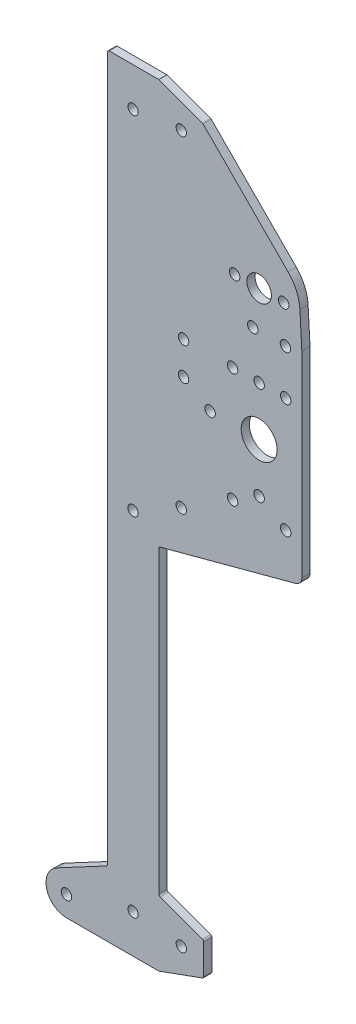
SolidWorks part; units mm, degrees
ref_plane "Front Plane" through (0, 0, 0) normal (0, 0, 1) x (1, 0, 0)
ref_plane "Top Plane" through (0, 0, 0) normal (0, 1, 0) x (1, 0, 0)
ref_plane "Right Plane" through (0, 0, 0) normal (1, 0, 0) x (0, 0, -1)
sketch "Sketch1" plane through (0, 0, 0) normal (0, 0, 1) x (1, 0, 0)
  line L1 (-10, 150) -> (10, 150)
  line L2 (-10, 150) -> (-10, -150)
  line L3 (-10, -150) -> (10, -150)
  line L4 (10, 150) -> (10, -150)
  line L5 (-10, 150) -> (10, -150) construction
  line L6 (-10, -150) -> (10, 150) construction
  point P0 (0, 0)
  dimension "D1" = 300
  dimension "20mm" = 20
extrude "Boss-Extrude1" add sketch "Sketch1" along normal blind 3.175
sketch "Sketch2" plane through (0, 0, 3.175) normal (0, 0, 1) x (1, 0, 0)
  line L0 (10, 150) -> (27.4625, 143.65)
  line L1 (27.4625, 143.65) -> (27.4625, 130.95)
  line L2 (27.4625, 130.95) -> (10, 124.6)
  line L3 (10, -150) -> (10, 150) construction
  line L4 (10, 124.6) -> (10, 150)
  line L5 (10, 150) -> (-10, 150) construction
  line L6 (-10, 0) -> (10, 0) construction
  line L7 (-10, 150) -> (-10, -150) construction
  line L8 (10, -124.6) -> (10, -150)
  line L9 (27.4625, -130.95) -> (10, -124.6)
  line L10 (27.4625, -143.65) -> (27.4625, -130.95)
  line L11 (10, -150) -> (27.4625, -143.65)
  line L12 (18.7312, 140.475) -> (18.7312, 134.125) construction
  circle A1 centre (18.7312, 134.125) radius 5 construction
  circle A2 centre (18.7312, 140.475) radius 2 construction
  circle A4 centre (18.7312, -134.125) radius 5 construction
  circle A5 centre (18.7312, -134.125) radius 2 construction
  circle A6 centre (18.7312, 137.3) radius 2
  circle A7 centre (18.7312, -137.3) radius 2
  point P3 (27.4625, 137.3)
  point P8 (10, 137.3)
  point P13 (18.7312, 127.775)
  point P31 (27.4625, -137.3)
  dimension "D3" = 4
  dimension "D4" = 10
  dimension "D1" = 17.4625
  dimension "2.5" = 25.4
  dimension "D2" = 12.7
  dimension "D5" = 9.525
  dimension "D6" = 9.525
extrude "Boss-Extrude2" add sketch "Sketch2" against normal up to surface (3.175 mm away) up to face at (0, 0, 0)
sketch "Sketch4" plane through (0, 0, 3.175) normal (0, 0, 1) x (1, 0, 0)
  line L0 (0, 150) -> (0, 135) construction
  line L2 (0, 135) -> (0, 0) construction
  line L3 (0, 0) -> (0, -135) construction
  line L4 (0, -135) -> (0, -150) construction
  line L6 (10, 150) -> (-10, 150) construction
  line L7 (-10, -150) -> (10, -150) construction
  circle A0 centre (0, -135) radius 2
  circle A1 centre (0, 0) radius 2
  circle A2 centre (0, 135) radius 2
  dimension "D4" = 4
  dimension "D1" = 15
  dimension "D2" = 135
  dimension "D3" = 135
extrude "Cut-Extrude1" cut sketch "Sketch4" against normal through all
sketch "Sketch5" plane through (0, 0, 3.175) normal (0, 0, 1) x (1, 0, 0)
  line L0 (-10, 111.9) -> (-41.75, 118.25)
  line L1 (-10, 150) -> (-10, -150) construction
  line L2 (-41.75, 118.25) -> (-41.75, 137.3)
  line L3 (-41.75, 137.3) -> (-10, 137.3)
  line L4 (-10, 137.3) -> (-10, 111.9)
  line L5 (10, 150) -> (-10, 150) construction
  line L6 (-41.75, 133.3313) -> (-37.7813, 133.3313) construction
  line L7 (-13.9688, 133.3313) -> (-10, 133.3313) construction
  line L8 (-10, -150) -> (-25.875, -150)
  line L9 (-29.6103, -135.0588) -> (-10, -124.6)
  line L10 (-10, -124.6) -> (-10, -150)
  circle A0 centre (-13.9688, 133.3313) radius 2.032
  circle A1 centre (-13.9688, 122.2188) radius 2.032
  circle A2 centre (-37.7813, 133.3313) radius 2.032
  circle A3 centre (-37.7813, 122.2188) radius 2.032
  arc A4 (-25.875, -150) -> (-29.6103, -135.0588) centre (-25.875, -142.0625) cw
  circle A5 centre (-25.875, -142.0625) radius 2.032
  point P24 (-25.875, 137.3)
  dimension "D5" = 4.064
  dimension "D9" = 4.064
  dimension "D10" = 7.9375
  dimension "D1" = 12.7
  dimension "D2" = 19.05
  dimension "D3" = 25.4
  dimension "D4" = 31.75
  dimension "D6" = 11.1125
  dimension "D7" = 23.8125
  dimension "D8" = 3.9688
  dimension "D11" = 25.4
extrude "Boss-Extrude3" [suppressed] add sketch "Sketch5" against normal up to surface (1.5875 mm away) up to face at (2, -135, 0)
fillet "Fillet3" [suppressed] radius 1.5875
sketch "Sketch6" plane through (0, 0, 3.175) normal (0, 0, 1) x (1, 0, 0)
  line L0 (-10, -124.6) -> (-10, -150) construction
  line L1 (-10, -150) -> (-25.875, -150) construction
  line L2 (-29.6103, -135.0588) -> (-10, -124.6) construction
  line L3 (-10, -124.6) -> (-10, -150)
  line L4 (-10, -150) -> (-25.875, -150)
  line L5 (-29.6103, -135.0588) -> (-10, -124.6)
  circle A0 centre (-25.875, -142.0625) radius 2.032 construction
  arc A1 (-29.6103, -135.0588) -> (-25.875, -150) centre (-25.875, -142.0625) ccw construction
  circle A2 centre (-25.875, -142.0625) radius 2.032
  arc A3 (-29.6103, -135.0588) -> (-25.875, -150) centre (-25.875, -142.0625) ccw
extrude "Boss-Extrude4" add sketch "Sketch6" against normal up to vertex (3.175 mm away) up to point (-10, -150, 0)
fillet "Fillet4" radius 0.7937 8 edges at (10, 124.6, 1.5875) (27.4625, 130.95, 1.5875) (-10, 150, 1.5875) (27.4625, 143.65, 1.5875) (-10, -124.6, 1.5875) (10, -124.6, 1.5875) (27.4625, -130.95, 1.5875) (27.4625, -143.65, 1.5875)
fillet "Fillet5" [suppressed] radius 1.5875
sketch "Sketch7" plane through (0, 0, 0) normal (0, 0, -1) x (-1, 0, 0)
  line L0 (-27.1212, 143.7462) -> (-65.2212, 117.3147)
  line L1 (-65.5625, 116.6625) -> (-65.5625, 10.1095)
  line L2 (-63.2093, 7.0427) -> (-10, -7.2147)
  line L4 (-10, -7.2147) -> (-10, 124.044)
  line L5 (-27.4625, 143.094) -> (-27.4625, 131.506) construction
  line L6 (-26.94, 130.76) -> (-10.5225, 124.79) construction
  line L7 (-27.4625, 143.094) -> (-27.4625, 131.506)
  line L8 (-26.94, 130.76) -> (-10.5225, 124.79)
  line L9 (-10, 150) -> (9.2063, 150) construction
  line L10 (-10, 150) -> (9.2063, 150) construction
  line L11 (-48.989, 45.225) -> (-48.989, 48.4) construction
  line L12 (-38.6703, 23) -> (-59.3078, 23) construction
  line L13 (-38.6703, 23) -> (-38.6703, 67.45) construction
  line L14 (-38.6703, 67.45) -> (-59.3078, 67.45) construction
  line L15 (-59.3078, 23) -> (-59.3078, 67.45) construction
  line L16 (-38.6703, 23) -> (-59.3078, 67.45) construction
  line L17 (-38.6703, 67.45) -> (-59.3078, 23) construction
  line L18 (-48.989, 99.2) -> (-48.989, 48.4) construction
  line L19 (-10, -124.044) -> (-10, 124.044) construction
  arc A0 (-65.2212, 117.3147) -> (-65.5625, 116.6625) centre (-64.7688, 116.6625) ccw
  arc A1 (-65.5625, 10.1095) -> (-63.2093, 7.0427) centre (-62.3875, 10.1095) ccw
  arc A2 (-26.94, 143.84) -> (-27.4625, 143.094) centre (-26.6688, 143.094) ccw construction
  arc A3 (-27.4625, 131.506) -> (-26.94, 130.76) centre (-26.6688, 131.506) ccw construction
  arc A4 (-10, 124.044) -> (-10.5225, 124.79) centre (-10.7937, 124.044) ccw construction
  arc A5 (-27.1212, 143.7462) -> (-27.4625, 143.094) centre (-26.6688, 143.094) ccw
  arc A6 (-27.4625, 131.506) -> (-26.94, 130.76) centre (-26.6688, 131.506) ccw
  arc A7 (-10, 124.044) -> (-10.5225, 124.79) centre (-10.7937, 124.044) ccw
  arc A8 (10, 149.2063) -> (9.2063, 150) centre (9.2063, 149.2063) ccw construction
  circle A9 centre (-48.989, 99.2) radius 4.7625
  circle A10 centre (-48.989, 48.4) radius 6.985
  circle A11 centre (-59.3078, 67.45) radius 2.032
  circle A12 centre (-59.3078, 23) radius 2.032
  circle A13 centre (-38.6703, 23) radius 2.032
  circle A14 centre (-38.6703, 67.45) radius 2.032
  circle A15 centre (-18.7312, 10.3) radius 2.032
  point P32 (-48.989, 45.225)
  point P45 (-18.7312, 137.3)
  dimension "D4" = 9.525
  dimension "D6" = 13.97
  dimension "D11" = 4.064
  dimension "D15" = 3.175
  dimension "D1" = 38.1
  dimension "D2" = 106.553
  dimension "D3" = 16.5735
  dimension "D5" = 50.8
  dimension "D7" = 3.175
  dimension "D8" = 44.45
  dimension "D9" = 50.8
  dimension "D10" = 20.6375
  dimension "D12" = 75
  dimension "D13" = 127
  dimension "D14" = 33.3375
extrude "Boss-Extrude5" add sketch "Sketch7" against normal up to surface (3.175 mm away) up to face at (2, -135, 3.175)
sketch "Sketch8" plane through (0, 0, 3.175) normal (0, 0, 1) x (1, 0, 0)
  line L0 (48.989, 48.4) -> (48.989, 67.45) construction
  line L1 (48.989, 48.4) -> (29.939, 48.4) construction
  line L2 (48.989, 48.4) -> (48.989, 29.35) construction
  line L3 (48.989, 99.2) -> (58.514, 99.2) construction
  line L4 (48.989, 99.2) -> (39.464, 99.2) construction
  line L5 (19.6203, 67.45) -> (19.6203, 54.75) construction
  circle A0 centre (48.989, 67.45) radius 2.032
  circle A1 centre (29.939, 48.4) radius 2.032
  circle A2 centre (48.989, 29.35) radius 2.032
  circle A3 centre (59.3078, 67.45) radius 2.032 construction
  circle A4 centre (58.514, 99.2) radius 2.032
  circle A5 centre (39.464, 99.2) radius 2.032
  circle A6 centre (19.6203, 54.75) radius 2.032
  circle A7 centre (19.6203, 67.45) radius 2.032
  point P20 (40.9949, 94.0213)
  point P21 (58.3131, 101.1458)
  dimension "D2" = 9.525
  dimension "D1" = 19.05
  dimension "D3" = 12.7
  dimension "D4" = 6.35
  dimension "D5" = 10.3187
extrude "Cut-Extrude2" cut sketch "Sketch8" against normal through all
sketch "Sketch9" plane through (0, 0, 0) normal (0, 0, -1) x (-1, 0, 0)
  line L0 (-27.2321, 143.6532) -> (-60.2559, 110.3836)
  line L2 (-65.5625, 86.5) -> (-64.8416, 100.0438)
  line L3 (-65.5625, 86.5) -> (-65.5625, 116.6625)
  line L4 (-27.1212, 143.7462) -> (-65.2212, 117.3147) construction
  line L5 (-27.1212, 143.7462) -> (-65.2212, 117.3147)
  line L6 (-65.5625, 116.6625) -> (-65.5625, 10.1095) construction
  arc A0 (-26.94, 143.84) -> (-27.1212, 143.7462) centre (-26.6688, 143.094) ccw construction
  arc A1 (-27.1212, 143.7462) -> (-27.2321, 143.6532) centre (-26.6688, 143.094) ccw
  arc A2 (-60.2559, 110.3836) -> (-64.8416, 100.0438) centre (-48.989, 99.2) ccw
  arc A4 (-65.2212, 117.3147) -> (-65.5625, 116.6625) centre (-64.7688, 116.6625) ccw construction
  arc A5 (-65.2212, 117.3147) -> (-65.5625, 116.6625) centre (-64.7688, 116.6625) ccw
  circle A6 centre (-59.3078, 67.45) radius 2.032 construction
  dimension "D1" = 15.875
  dimension "D2" = 19.05
extrude "Cut-Extrude3" cut sketch "Sketch9" against normal through all
sketch "Sketch10" plane through (0, 0, 0) normal (0, 0, -1) x (-1, 0, 0)
  line L0 (-59.2125, 84.9125) -> (-46.5125, 84.9125) construction
  line L1 (-65.5625, 86.5) -> (-65.5625, 10.1095) construction
  circle A0 centre (-59.2125, 84.9125) radius 2.032
  circle A1 centre (-46.5125, 84.9125) radius 2.032
  circle A2 centre (-59.3078, 67.45) radius 2.032 construction
  point P6 (-48.989, 67.45)
  dimension "D1" = 12.7
  dimension "D2" = 17.4625
  dimension "D3" = 6.35
extrude "Cut-Extrude4" cut sketch "Sketch10" against normal through all
